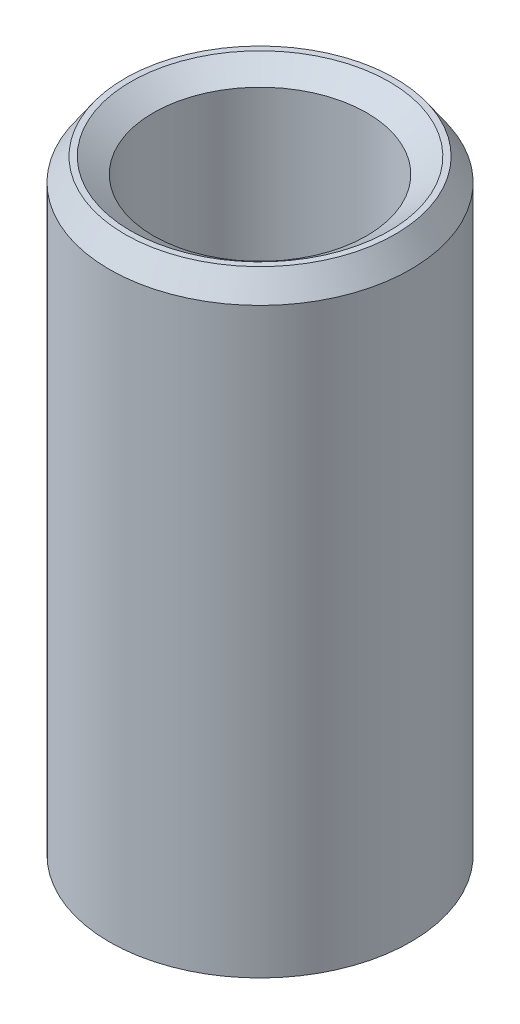
SolidWorks part; units mm, degrees
ref_plane "Front Plane" through (0, 0, 0) normal (0, 0, 1) x (1, 0, 0)
ref_plane "Top Plane" through (0, 0, 0) normal (0, 1, 0) x (1, 0, 0)
ref_plane "Right Plane" through (0, 0, 0) normal (1, 0, 0) x (0, 0, -1)
sketch "Sketch1" plane through (0, 0, 0) normal (0, 1, 0) x (1, 0, 0)
  circle A0 centre (0, 0) radius 15
  dimension "SLEEVE_OD" = 30
extrude "Boss-Extrude1" add sketch "Sketch1" along normal blind 61.7826
sketch "Sketch2" plane through (0, 0, 0) normal (0, 1, 0) x (1, 0, 0)
  circle A0 centre (0, 0) radius 10.6175
  dimension "BORE_D" = 21.235
extrude "Cut-Extrude1" cut sketch "Sketch2" along normal through all
chamfer "Chamfer1" distance 2.2511 angle 34.519 4 edges at (0, 61.7826, 10.6175) (0, 0, 10.6175) (0, 0, 15) (0, 61.7826, 15) first distance on face at (0, 61.7826, 10.6175) first distance on face at (0, 0, 10.6175) first distance on face at (0, 61.7826, 15)
